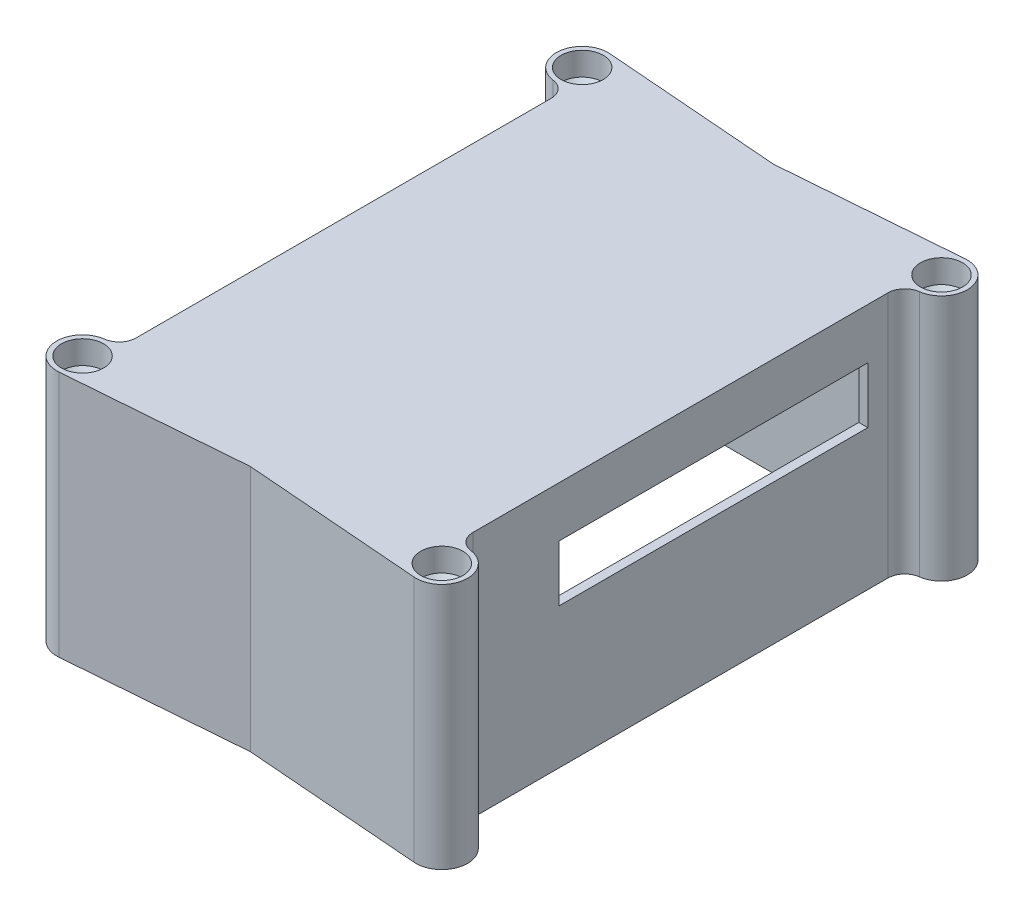
SolidWorks part; units mm, degrees
material "PP Copolymer"
ref_plane "Front Plane" through (0, 0, 0) normal (0, 0, 1) x (1, 0, 0)
ref_plane "Top Plane" through (0, 0, 0) normal (0, 1, 0) x (1, 0, 0)
ref_plane "Right Plane" through (0, 0, 0) normal (1, 0, 0) x (0, 0, -1)
sketch "Sketch1" plane through (0, 0, 0) normal (0, 1, 0) x (1, 0, 0)
  line L1 (-30, 44.5) -> (30, 44.5)
  line L2 (-30, 44.5) -> (-30, -44.5)
  line L3 (-30, -44.5) -> (30, -44.5)
  line L4 (30, 44.5) -> (30, -44.5)
  line L5 (-30, 44.5) -> (30, -44.5) construction
  line L6 (-30, -44.5) -> (30, 44.5) construction
  point P0 (0, 0)
  dimension "D1" = 60
  dimension "D2" = 89
extrude "BASE" add sketch "Sketch1" along normal blind 9 and the other way blind 35
fillet "OUTSIDE OF BASE" radius 3 4 edges at (-30, -13, -44.5) (30, -13, -44.5) (30, -13, 44.5) (-30, -13, 44.5)
shell "INSIDE OF BASE" thickness 1.6 removed face at (0, -35, 0)
sketch "RPI 3 B + BASE PROFILE" plane through (0, 7.4, 0) normal (0, -1, 0) x (-1, 0, 0)
  line L1 (28, -42.5) -> (-28, -42.5)
  line L2 (28, -42.5) -> (28, 42.5)
  line L3 (28, 42.5) -> (-28, 42.5)
  line L4 (-28, -42.5) -> (-28, 42.5)
  line L5 (28, -42.5) -> (-28, 42.5) construction
  line L6 (28, 42.5) -> (-28, -42.5) construction
  point P0 (0, 0)
  dimension "D1" = 56
  dimension "D2" = 85
ref_plane "ETHERNET PORT REFERENCE PLANE" through (0, 0, 42.5) normal (0, 0, 1) x (1, 0, 0)
sketch "FASTENER POINTS" plane through (0, 7.4, 0) normal (0, -1, 0) x (-1, 0, 0)
  line L0 (28, 42.5) -> (-28, 42.5) construction
  line L1 (-24.5, 39) -> (24.5, 39) construction
  line L2 (-24.5, 39) -> (-24.5, -19) construction
  line L3 (-24.5, -19) -> (24.5, -19) construction
  line L4 (24.5, 39) -> (24.5, -19) construction
  line L5 (0, 39) -> (0, 42.5) construction
  point P0 (-24.5, 39)
  point P6 (-24.5, -19)
  point P7 (24.5, 39)
  point P8 (24.5, -19)
  dimension "D1" = 49
  dimension "D2" = 58
  dimension "D3" = 3.5
sketch "Sketch22" plane through (0, -35, 0) normal (0, -1, 0) x (1, 0, 0)
  line L3 (-31.6414, 49.086) -> (27, 44.5)
  line L8 (-27, 44.5) -> (27, 44.5)
  line L10 (-30, 41.5) -> (-30, 39.7295)
  line L11 (-30, -41.5) -> (-30, 41.5) construction
  line L12 (-30, 39.7295) -> (-32.3586, 39.914)
  line L14 (-27, 44.5) -> (27, 44.5) construction
  arc A1 (-27, 44.5) -> (-30, 41.5) centre (-27, 41.5) ccw construction
  arc A2 (-27, 44.5) -> (-30, 41.5) centre (-27, 41.5) ccw
  arc A3 (-32.3586, 39.914) -> (-31.6414, 49.086) centre (-32, 44.5) cw
  dimension "D1" = 4.6
  dimension "D3" = 2
extrude "TOP FASTENING BODY" add sketch "Sketch22" against normal up to surface (44 mm away) up to face at (0, 9, 0)
hole_wizard "CBORE for M4 SHCS1" positions "Sketch23" profile "Sketch24" counterbore size "M4" standard "ANSI Metric" end condition through all
sketch "Sketch23" plane through (0, 9, 0) normal (0, 1, 0) x (1, 0, 0)
  arc A1 (-32.3586, -39.914) -> (-31.6414, -49.086) centre (-32, -44.5) ccw construction
  point P0 (-32, -44.5)
sketch "Sketch24" plane through (-32, 9, 44.5) normal (1, 0, 0) x (0, 0, 1)
  line L0 (0, 0) -> (0, 44)
  line L1 (0, 44) -> (2.4, 44)
  line L3 (2.4, 44) -> (2.4, 4)
  line L4 (2.4, 4) -> (3.75, 4)
  line L5 (3.75, 4) -> (3.75, 0)
  line L7 (3.75, 0) -> (0, 0)
  line L11 (0, -6.35) -> (0, 107.95) construction
  dimension "Thru Hole Dia." = 4.8
  dimension "Thru Hole Depth" = 44
  dimension "C'Bore Dia." = 7.5
  dimension "C'Bore Depth" = 4
mirror "TFB M H" about plane through (0, 0, 0) normal (1, 0, 0) of "CBORE for M4 SHCS1", "TOP FASTENING BODY"
mirror "TFB M V" about plane through (0, 0, 0) normal (0, 0, 1) of "TFB M H", "CBORE for M4 SHCS1", "TOP FASTENING BODY"
sketch "Sketch12" plane through (-30, 0, 0) normal (-1, 0, 0) x (0, 0, 1)
  line L1 (-36.1, -31.5) -> (-27.7, -31.5)
  line L2 (-36.1, -31.5) -> (-36.1, -35)
  line L3 (-36.1, -35) -> (-27.7, -35)
  line L4 (-27.7, -31.5) -> (-27.7, -35)
  line L5 (-36.1, -31.5) -> (-27.7, -35) construction
  line L6 (-36.1, -35) -> (-27.7, -31.5) construction
  line L7 (-41.5, -35) -> (41.5, -35) construction
  point P0 (-31.9, -33.25)
  dimension "D1" = 8.4
  dimension "D2" = 3.5
  dimension "D3" = 10.6
extrude "MICROUSB" cut sketch "Sketch12" against normal up to surface (1.6 mm away) up to face at (-28.4, -13.8, 0)
chamfer "3D PRINTING FOR FASTENING FEATURE " distance 1.5 angle 45 4 edges at (32, 5, 46.9) (32, 5, -42.1) (-32, 5, -42.1) (-32, 5, 46.9)
fillet "TFB OUTER" radius 3 4 edges at (30, -13, 39.7295) (30, -13, -39.7295) (-30, -13, -39.7295) (-30, -13, 39.7295)
sketch "Sketch27" plane through (0, -35, 0) normal (0, -1, 0) x (1, 0, 0)
sketch "Sketch28" plane through (30, 0, 0) normal (1, 0, 0) x (0, 0, -1)
  line L1 (33.3779, 0) -> (-21.6221, 0)
  line L2 (33.3779, 0) -> (33.3779, -10)
  line L3 (33.3779, -10) -> (-21.6221, -10)
  line L4 (-21.6221, 0) -> (-21.6221, -10)
  dimension "D1" = 55
  dimension "D2" = 10
extrude "Cut-Extrude1" cut sketch "Sketch28" against normal blind 10
sketch "Sketch30" plane through (0, -35, 0) normal (0, -1, 0) x (1, 0, 0)
